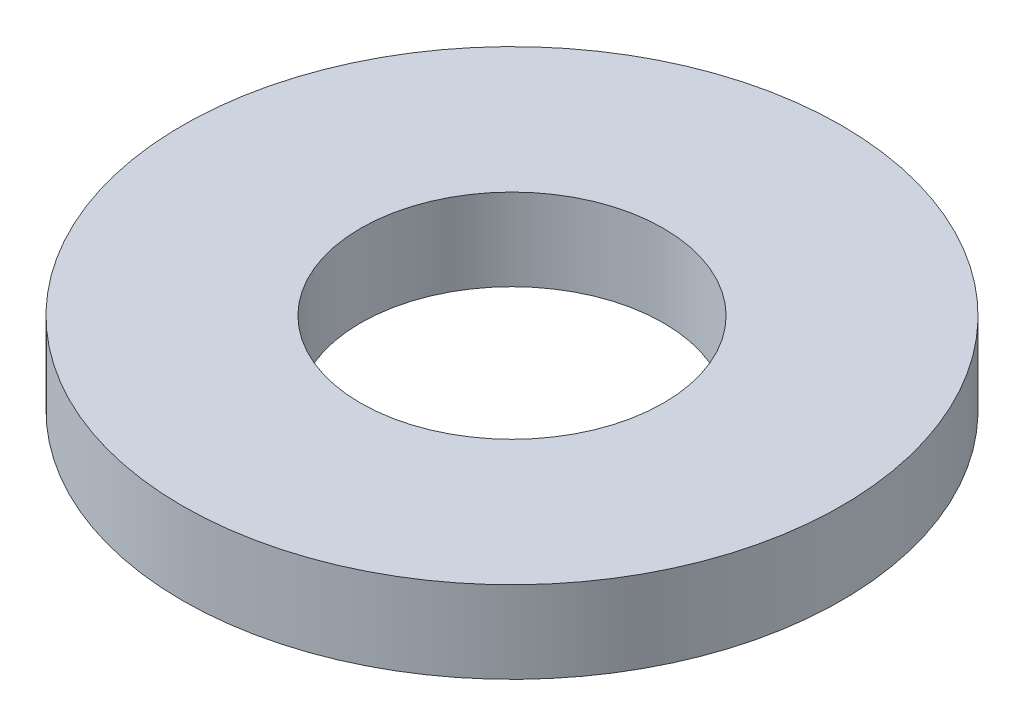
SolidWorks part; units mm, degrees
ref_plane "Front Plane" through (0, 0, 0) normal (0, 0, 1) x (1, 0, 0)
ref_plane "Top Plane" through (0, 0, 0) normal (0, 1, 0) x (1, 0, 0)
ref_plane "Right Plane" through (0, 0, 0) normal (1, 0, 0) x (0, 0, -1)
sketch "Sketch1" plane through (0, 0, 0) normal (0, 1, 0) x (1, 0, 0)
  circle A0 centre (0, 0) radius 92.5
  dimension "FLANGE_OD" = 185
extrude "Boss-Extrude1" add sketch "Sketch1" along normal blind 23
sketch "Sketch2" plane through (0, 0, 0) normal (0, 1, 0) x (1, 0, 0)
  circle A0 centre (0, 0) radius 42.5
  dimension "BORE_D" = 85
extrude "Cut-Extrude1" cut sketch "Sketch2" along normal through all
sketch "Sketch3" plane through (0, 23, 0) normal (0, 1, 0) x (1, 0, 0)
  circle A0 centre (0, 0) radius 29.2778 construction
  circle A1 centre (-29.2778, 0) radius 8.422
  dimension "BOLT_D" = 16.844
  dimension "BOLT_PCD" = 58.5556
extrude "Cut-Extrude2" cut sketch "Sketch3" against normal blind 19.7447 rebuild error yes
pattern_circular "CirPattern1" count 5 over 360 rebuild error yes
